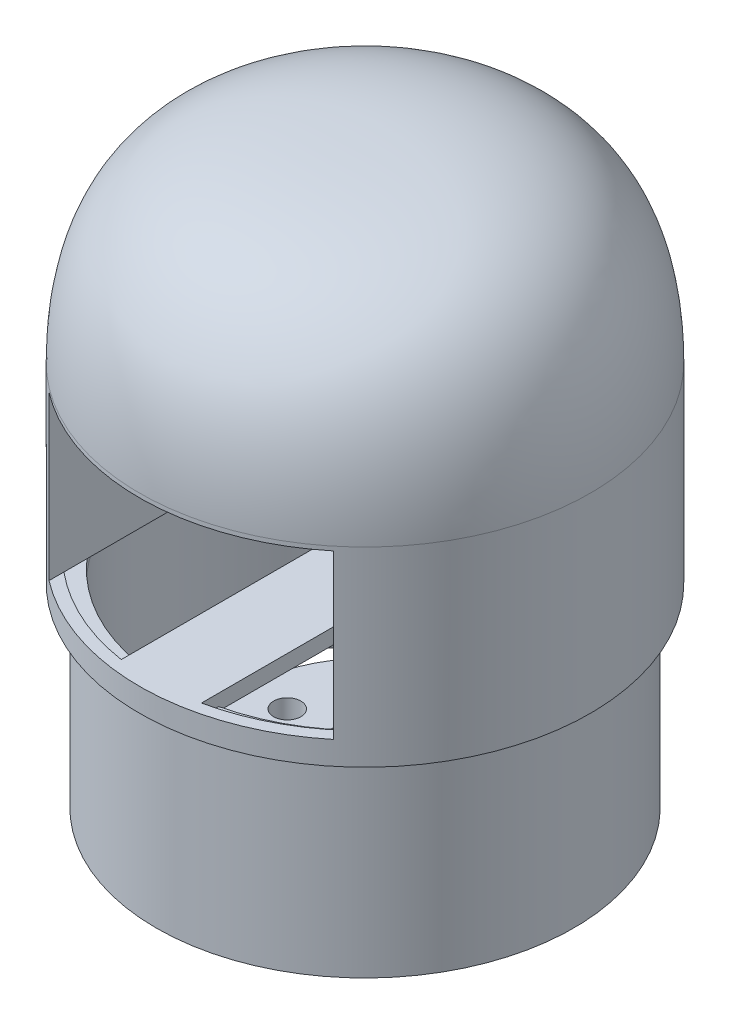
SolidWorks part; units mm, degrees
ref_plane "Front Plane" through (0, 0, 0) normal (0, 0, 1) x (1, 0, 0)
ref_plane "Top Plane" through (0, 0, 0) normal (0, 1, 0) x (1, 0, 0)
ref_plane "Right Plane" through (0, 0, 0) normal (1, 0, 0) x (0, 0, -1)
sketch "Sketch1" plane through (0, 0, 0) normal (0, 1, 0) x (1, 0, 0)
  circle A0 centre (0, 0) radius 25.35
  circle A1 centre (0, 0) radius 26.85
  dimension "D1" = 53.7
  dimension "D2" = 1.5
extrude "Boss-Extrude3" add sketch "Sketch1" along normal blind 25
sketch "Sketch3" plane through (0, 0, 0) normal (0, -1, 0) x (1, 0, 0)
  line L0 (-25.35, 0) -> (25.35, 0) construction
  line L1 (0, 25.35) -> (0, -25.35) construction
  line L2 (-25.0324, 4) -> (-14.4568, 4)
  line L3 (-4, 14.4568) -> (-4, 25.0324)
  line L4 (14.4568, 4) -> (25.0324, 4)
  line L5 (4, 25.0324) -> (4, 14.4568)
  line L6 (4, -14.4568) -> (4, -25.0324)
  line L7 (25.0324, -4) -> (14.4568, -4)
  line L8 (-14.4568, -4) -> (-25.0324, -4)
  line L9 (-4, -25.0324) -> (-4, -14.4568)
  circle A0 centre (0, 0) radius 25.35 construction
  arc A1 (-25.0324, 4) -> (-25.0324, -4) centre (0, 0) ccw
  arc A2 (4, 25.0324) -> (-4, 25.0324) centre (0, 0) ccw
  arc A3 (25.0324, -4) -> (25.0324, 4) centre (0, 0) ccw
  arc A4 (-4, -25.0324) -> (4, -25.0324) centre (0, 0) ccw
  circle A5 centre (-10, 0) radius 1.75
  circle A6 centre (0, 10) radius 1.75
  circle A7 centre (10, 0) radius 1.75
  circle A8 centre (0, -10) radius 1.75
  circle A9 centre (0, 0) radius 5
  arc A10 (-14.4568, -4) -> (-4, -14.4568) centre (0, 0) ccw
  arc A11 (-4, 14.4568) -> (-14.4568, 4) centre (0, 0) ccw
  arc A12 (14.4568, 4) -> (4, 14.4568) centre (0, 0) ccw
  arc A13 (4, -14.4568) -> (14.4568, -4) centre (0, 0) ccw
  point P22 (0, 0)
  point P32 (0, 0)
  dimension "D4" = 3.5
  dimension "D7" = 10
  dimension "D8" = 30
  dimension "D1" = 4
  dimension "D2" = 4
  dimension "D5" = 10
  dimension "D3" = 4
  dimension "D6" = 4
extrude "Boss-Extrude4" add sketch "Sketch3" against normal blind 6
ref_plane "Plane1" through (0, 0, 0) normal (0, 0, 1) x (1, 0, 0)
sketch "Sketch4" plane through (0, 0, 0) normal (0, 0, 1) x (1, 0, 0)
  line L0 (0, 0) -> (0, 105.4419) construction
  line L1 (-26.85, 25) -> (-29, 25)
  line L2 (26.85, 25) -> (-26.85, 25) construction
  line L3 (-20.2823, 75) -> (15.9379, 75) construction
  line L4 (25.35, 25) -> (-25.35, 25) construction
  line L5 (-29, 25) -> (-29, 49.5305)
  line L6 (-29, 49.5305) -> (-29, 72.1402) construction
  line L7 (-29, 72.1402) -> (-14.5225, 75) construction
  line L8 (-14.5225, 75) -> (0, 75) construction
  line L9 (-29, 46.0581) -> (-29, 86.8306) construction
  line L10 (-26.85, 26.5) -> (-27.5, 26.5)
  line L11 (-27.5, 26.5) -> (-27.5, 49.5305)
  line L12 (-26.85, 26.5) -> (-25.3371, 26.5)
  line L13 (-25.3371, 26.5) -> (-25.3371, 25)
  line L14 (-25.3371, 25) -> (-26.85, 25)
  line L15 (0, 75) -> (0, 73.5)
  line L16 (0, 75) -> (0, 73.5)
  spline S0 degree 3 poles (-29, 49.5305) (-29, 72.1402) (-14.5225, 75) (0, 75) knots 0 0 0 0 1 1 1 1
  spline S1 degree 1 poles (-27.5, 49.5305) (0, 73.5) knots 0 0 1 1 construction
  spline S2 degree 3 poles (-27.5, 49.5305) (-27.5, 50.1973) (-27.4725, 51.5589) (-27.312, 54.0541) (-26.9217, 56.9112) (-26.1775, 59.8972) (-25.1851, 62.4837) (-23.97, 64.7018) (-22.0795, 67.2198) (-19.2427, 69.6414) (-15.1447, 71.6218) (-10.4558, 72.8282) (-5.3614, 73.4116) (-1.7719, 73.5) (0, 73.5) knots 0 0 0 0 0.03125 0.0625 0.125 0.1875 0.25 0.3125 0.375 0.5 0.625 0.75 0.875 1 1 1 1
  dimension "D1" = 50
  dimension "D2" = 29
  dimension "D3" = 1.5
revolve "Revolve1" add sketch "Sketch4" angle 360 about L0 region at (-27.925, 25.578, 0)
sketch "Sketch5" plane through (0, 0, 0) normal (0, 0, 1) x (1, 0, 0)
  line L0 (0, 81.0379) -> (0.5211, 24.0117) construction
  line L1 (27.5, 26.5) -> (-27.5, 26.5) construction
  line L2 (-17.6113, 28) -> (18.3887, 28)
  line L3 (-17.6113, 28) -> (-17.6113, 49)
  line L4 (-17.6113, 49) -> (18.3887, 49)
  line L5 (18.3887, 28) -> (18.3887, 49)
  line L6 (-17.6113, 28) -> (18.3887, 49) construction
  line L7 (-17.6113, 49) -> (18.3887, 28) construction
  point P2 (0.3887, 38.5)
  dimension "D1" = 12
  dimension "D2" = 21
  dimension "D3" = 36
extrude "Cut-Extrude1" cut sketch "Sketch5" against normal through all both and the other way through all
sketch "Sketch6" plane through (0, 0, 0) normal (0, 0, 1) x (1, 0, 0)
  line L6 (-19.6113, 28) -> (-17.6113, 28)
  line L7 (18.3887, 28) -> (-17.6113, 28) construction
  line L8 (-4.17, 28) -> (5.83, 28)
  line L9 (5.83, 28) -> (5.83, 26)
  line L10 (5.83, 26) -> (-4.17, 26)
  line L11 (-4.17, 26) -> (-4.17, 28)
  line L14 (-17.6113, 28) -> (-17.6113, 49)
  line L15 (-17.6113, 49) -> (-19.6113, 49)
  line L16 (-19.6113, 49) -> (-19.6113, 28)
  line L17 (-4.17, 49) -> (-4.17, 51)
  line L18 (-17.6113, 49) -> (18.3887, 49) construction
  line L19 (-4.17, 51) -> (5.83, 51)
  line L20 (5.83, 51) -> (5.83, 49)
  line L21 (5.83, 49) -> (-4.17, 49)
  dimension "D1" = 2
  dimension "D2" = 2
  dimension "D4" = 2
  dimension "D5" = 10
extrude "Boss-Extrude6" add sketch "Sketch6" against normal up to next and the other way up to next
